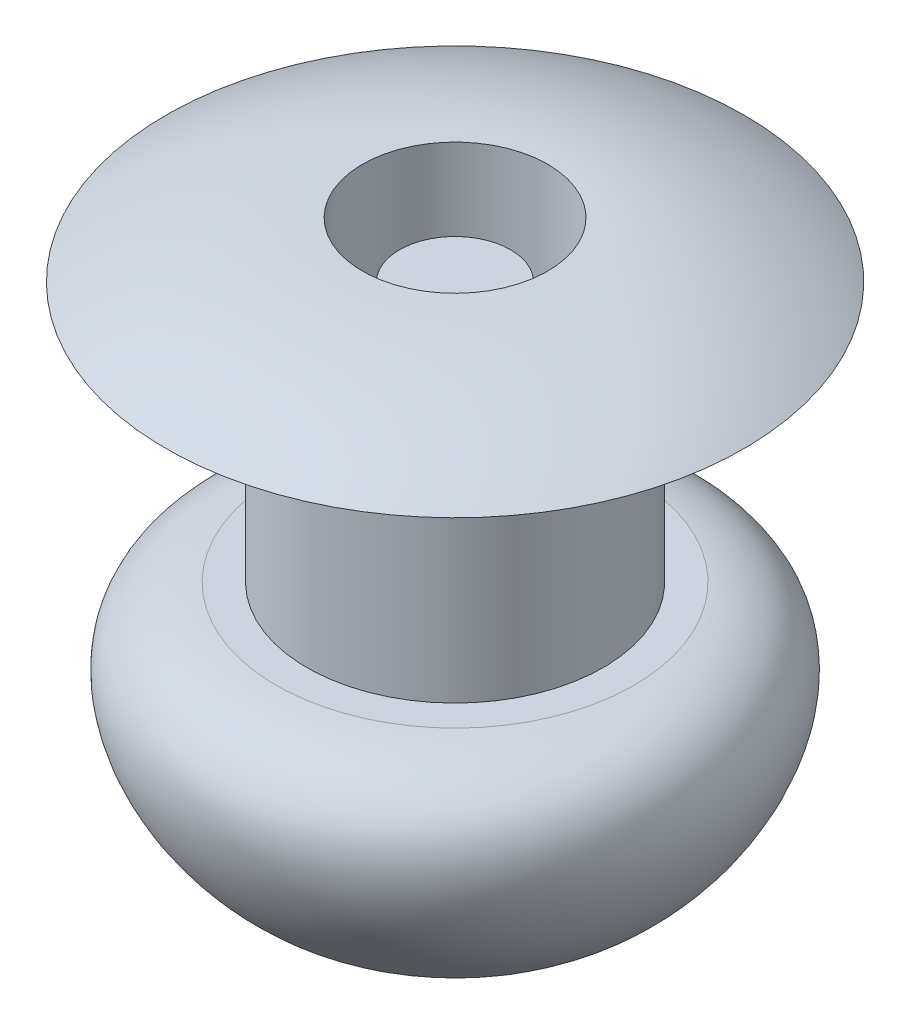
SolidWorks part; units mm, degrees
material "AISI 316 Stal nierdzewna odprężona (SS)"
ref_plane "Płaszczyzna przednia" through (0, 0, 0) normal (0, 0, 1) x (1, 0, 0)
ref_plane "Płaszczyzna górna" through (0, 0, 0) normal (0, 1, 0) x (1, 0, 0)
ref_plane "Płaszczyzna prawa" through (0, 0, 0) normal (1, 0, 0) x (0, 0, -1)
sketch "Szkic1" plane through (0, 0, 0) normal (1, 0, 0) x (0, 0, -1)
  line L1 (0, 0) -> (-0.75, 0)
  line L2 (-0.75, 0) -> (-0.75, -3.7103)
  line L3 (-0.75, -3.7103) -> (-1.25, -3.7103)
  line L4 (-1.25, -3.7103) -> (-1.25, 0.75)
  line L5 (-3.9, 0) -> (-2, 0)
  line L6 (-2, 0) -> (-2, -3.5096)
  line L7 (-2, -3.5096) -> (-2.4139, -3.5096)
  line L8 (0, 0) -> (0, 0.75) construction
  line L9 (0, -3.7103) -> (0, 0)
  line L10 (0, -3.7103) -> (0, -5.2103)
  arc A0 (-1.25, 0.75) -> (-3.9, 0) centre (-1.25, -4.3067) ccw
  ellipse E0 centre (0, -4.4603) end of major axis (1.75, -4.4603) minor radius 0.75 (-0.956, -5.0885) -> (0, -5.2103) ccw
  spline S0 degree 3 poles (-2.4139, -3.5096) (-3.8675, -3.6792) (-3.5289, -5.8116) (-1.084, -7.3831) (-0.2718, -5.3845) (-0.956, -5.0885) knots 0 0 0 0 0.464993 0.721928 1 1 1 1
  point P1 (0, 0)
  point P14 (0, -6.6839)
  point P15 (0, 0)
  dimension "D1" = 7.8
  dimension "D2" = 2.5
  dimension "D3" = 4
  dimension "D4" = 0.75
  dimension "D5" = 1.5
  dimension "D6" = 1.5
  dimension "D7" = 3.5
  dimension "D8" = 3.1855
  dimension "D9" = 2.5026
  dimension "D10" = 1.9
  dimension "D11" = 1.5789
  dimension "D12" = 0.5792
  dimension "D13" = 4.8278
  dimension "D14" = 3.3858
  dimension "D15" = 2.8395
  dimension "D16" = 1.25
  dimension "D17" = 0.6409
  dimension "D18" = 0.956
revolve "Obrót1" add sketch "Szkic1" angle 360 about L8
